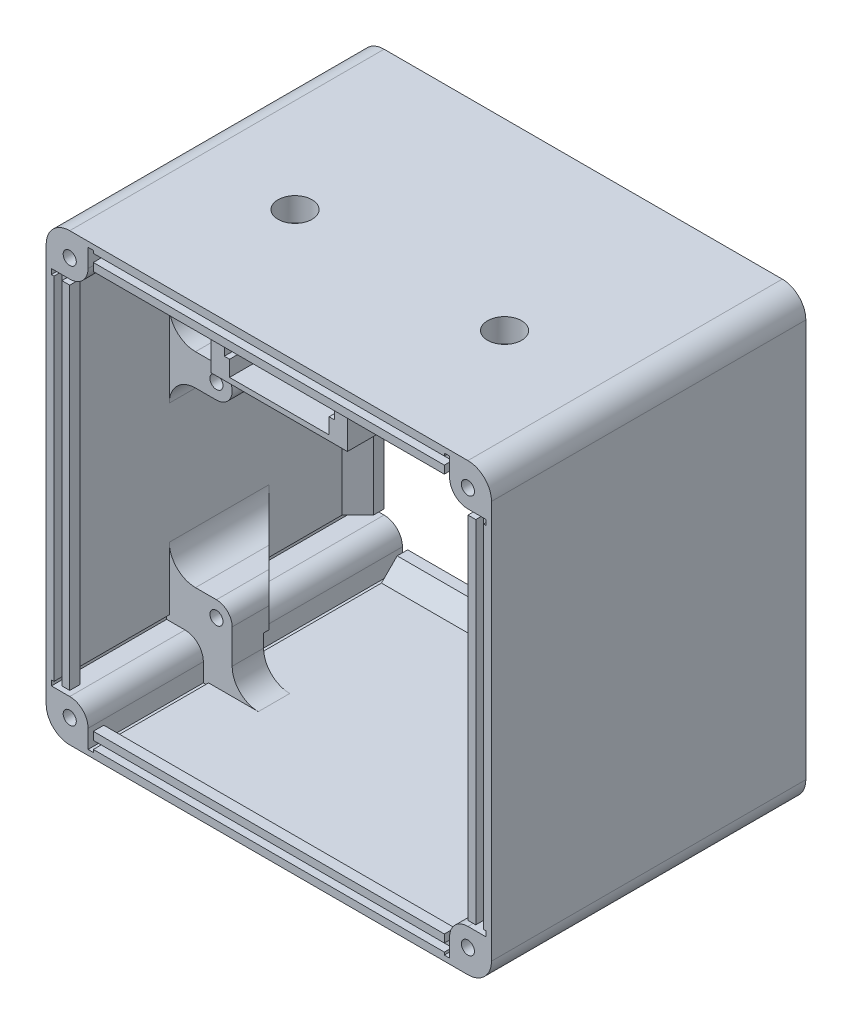
SolidWorks part; units mm, degrees
ref_plane "Front Plane" through (0, 0, 0) normal (0, 0, 1) x (1, 0, 0)
ref_plane "Top Plane" through (0, 0, 0) normal (0, 1, 0) x (1, 0, 0)
ref_plane "Right Plane" through (0, 0, 0) normal (1, 0, 0) x (0, 0, -1)
sketch "Sketch1" plane through (0, 0, 0) normal (0, 0, 1) x (1, 0, 0)
  line L1 (-42.5, -42.5) -> (42.5, -42.5)
  line L2 (-42.5, -42.5) -> (-42.5, 42.5)
  line L3 (-42.5, 42.5) -> (42.5, 42.5)
  line L4 (42.5, -42.5) -> (42.5, 42.5)
  line L5 (-42.5, -42.5) -> (42.5, 42.5) construction
  line L6 (-42.5, 42.5) -> (42.5, -42.5) construction
  point P0 (0, 0)
  dimension "D1" = 85
  dimension "D2" = 85
extrude "Boss-Extrude1" add sketch "Sketch1" along normal blind 60
sketch "Sketch8" plane through (0, 0, 0) normal (0, 0, -1) x (-1, 0, 0)
  line L14 (41, -41) -> (41, 41)
  line L15 (-41, -41) -> (41, -41)
  line L16 (-41, 41) -> (-41, -41)
  line L17 (41, 41) -> (-41, 41)
  line L18 (41, -36.5) -> (41, 36.5)
  line L19 (-36.5, -41) -> (36.5, -41)
  line L20 (-41, 36.5) -> (-41, -36.5)
  line L21 (36.5, 41) -> (-36.5, 41)
  arc A0 (-36.5, -41) -> (-41, -36.5) centre (-36.5, -36.5) cw
  arc A1 (41, -36.5) -> (36.5, -41) centre (36.5, -36.5) cw
  arc A2 (41, 36.5) -> (36.5, 41) centre (36.5, 36.5) ccw
  arc A3 (-41, 36.5) -> (-36.5, 41) centre (-36.5, 36.5) cw
  dimension "D2" = 4.5
  dimension "D1" = 1.5
extrude "Cut-Extrude4" cut sketch "Sketch8" against normal through all
fillet "Fillet4" radius 6 4 edges at (42.5, 42.5, 30) (42.5, -42.5, 30) (-42.5, 42.5, 30) (-42.5, -42.5, 30)
sketch "Sketch34" plane through (0, 0, 0) normal (0, 0, 1) x (1, 0, 0)
  line L0 (36.5, 42.5) -> (-36.5, 42.5) construction
  line L1 (-42.5, 36.5) -> (-42.5, -36.5) construction
  line L2 (-36.5, -42.5) -> (36.5, -42.5) construction
  line L3 (36.5, 42.5) -> (-36.5, 42.5)
  line L4 (42.5, -36.5) -> (42.5, 36.5)
  line L5 (36.5, 42.5) -> (-36.5, 42.5)
  line L6 (-42.5, 36.5) -> (-42.5, -36.5)
  line L7 (-36.5, -42.5) -> (36.5, -42.5)
  line L8 (42.5, -36.5) -> (42.5, 36.5)
  line L9 (36.5, 42.5) -> (-36.5, 42.5)
  line L10 (-42.5, 36.5) -> (-42.5, -36.5)
  line L11 (-36.5, -42.5) -> (36.5, -42.5)
  line L12 (-42.5, 36.5) -> (-42.5, -36.5)
  line L13 (-36.5, -42.5) -> (36.5, -42.5)
  line L14 (36.5, 38) -> (-36.5, 38)
  line L15 (-38, 36.5) -> (-38, -36.5)
  line L16 (-36.5, -38) -> (36.5, -38)
  line L17 (38, -36.5) -> (38, 36.5)
  arc A0 (-36.5, 42.5) -> (-42.5, 36.5) centre (-36.5, 36.5) ccw construction
  arc A1 (-42.5, -36.5) -> (-36.5, -42.5) centre (-36.5, -36.5) ccw construction
  arc A2 (36.5, -42.5) -> (42.5, -36.5) centre (36.5, -36.5) ccw construction
  arc A3 (-36.5, 42.5) -> (-42.5, 36.5) centre (-36.5, 36.5) ccw
  arc A4 (42.5, 36.5) -> (36.5, 42.5) centre (36.5, 36.5) ccw
  arc A5 (-36.5, 42.5) -> (-42.5, 36.5) centre (-36.5, 36.5) ccw
  arc A6 (-42.5, -36.5) -> (-36.5, -42.5) centre (-36.5, -36.5) ccw
  arc A7 (36.5, -42.5) -> (42.5, -36.5) centre (36.5, -36.5) ccw
  arc A8 (42.5, 36.5) -> (36.5, 42.5) centre (36.5, 36.5) ccw
  arc A9 (-36.5, 42.5) -> (-42.5, 36.5) centre (-36.5, 36.5) ccw
  arc A10 (-42.5, -36.5) -> (-36.5, -42.5) centre (-36.5, -36.5) ccw
  arc A11 (36.5, -42.5) -> (42.5, -36.5) centre (36.5, -36.5) ccw
  arc A12 (-42.5, -36.5) -> (-36.5, -42.5) centre (-36.5, -36.5) ccw
  arc A13 (36.5, -42.5) -> (42.5, -36.5) centre (36.5, -36.5) ccw
  arc A14 (-36.5, 38) -> (-38, 36.5) centre (-36.5, 36.5) ccw
  arc A15 (-38, -36.5) -> (-36.5, -38) centre (-36.5, -36.5) ccw
  arc A16 (36.5, -38) -> (38, -36.5) centre (36.5, -36.5) ccw
  arc A17 (38, 36.5) -> (36.5, 38) centre (36.5, 36.5) ccw
  dimension "D1" = 0
  dimension "D2" = 4.5
extrude "Boss-Extrude11" add sketch "Sketch34" along normal blind 2 contours L11 A11 L8 A8 L3 A3 L10 A10 A17 L17 A16 L16 A15 L15 A14 L14 region at (39.8926, 39.8926, 0)
sketch "Sketch35" plane through (0, 0, 0) normal (0, 0, -1) x (-1, 0, 0)
  line L25 (-36.5, -41) -> (36.5, -41)
  line L26 (41, -36.5) -> (41, 36.5)
  line L27 (36.5, 41) -> (-36.5, 41)
  line L28 (-41, 36.5) -> (-41, -36.5)
  line L29 (-36.5, -41) -> (36.5, -41)
  line L30 (41, -36.5) -> (41, 36.5)
  line L31 (36.5, 41) -> (-36.5, 41)
  line L32 (-41, 36.5) -> (-41, -36.5)
  arc A20 (-41, -36.5) -> (-36.5, -41) centre (-36.5, -36.5) ccw
  arc A21 (36.5, -41) -> (41, -36.5) centre (36.5, -36.5) ccw
  arc A22 (41, 36.5) -> (36.5, 41) centre (36.5, 36.5) ccw
  arc A23 (-36.5, 41) -> (-41, 36.5) centre (-36.5, 36.5) ccw
  arc A24 (-41, -36.5) -> (-36.5, -41) centre (-36.5, -36.5) ccw
  arc A25 (36.5, -41) -> (41, -36.5) centre (36.5, -36.5) ccw
  arc A26 (41, 36.5) -> (36.5, 41) centre (36.5, 36.5) ccw
  arc A27 (-36.5, 41) -> (-41, 36.5) centre (-36.5, 36.5) ccw
  dimension "D1" = 1.5
extrude "Cut-Extrude-Thin2" cut sketch "Sketch35" against normal blind 1.5 thin thin type one direction reverse wall 1.5
ref_plane "Plane1" through (0, 0, 30) normal (0, 0, 1) x (1, 0, 0)
mirror "Mirror8" about plane through (0, 0, 30) normal (0, 0, 1) of "Boss-Extrude11", "Cut-Extrude-Thin2"
chamfer "Chamfer5" distance 3 angle 45 16 edges at (0, -41, 58) (39.682, -39.682, 58) (-39.682, -39.682, 58) (41, 0, 58) (-41, 0, 58) (39.682, 39.682, 58) (-39.682, 39.682, 58) (0, 41, 58) (0, -41, 2) (-39.682, -39.682, 2) (39.682, -39.682, 2) (-41, 0, 2) (41, 0, 2) (-39.682, 39.682, 2) (39.682, 39.682, 2) (0, 41, 2)
sketch "Sketch14" plane through (0, 0, 60) normal (0, 0, 1) x (1, 0, 0)
  line L0 (-42.5, 36.5) -> (-42.5, -36.5) construction
  line L1 (-38, 33.5) -> (-42.5, 33.5)
  line L2 (-42.5, 36.5) -> (-42.5, -36.5) construction
  line L3 (-42.5, 33.5) -> (-42.5, 38)
  line L4 (-38, 42.5) -> (-33.5, 42.5)
  line L5 (-33.5, 42.5) -> (-33.5, 38)
  arc A0 (-38, 42.5) -> (-42.5, 38) centre (-38, 38) ccw
  arc A2 (-38, 33.5) -> (-33.5, 38) centre (-38, 38) ccw
  dimension "D1" = 38
  dimension "D2" = 38
extrude "Boss-Extrude6" add sketch "Sketch14" against normal up to surface (60 mm away) up to face at (0, 0, 0)
sketch "Sketch15" plane through (0, 0, 0) normal (0, 0, -1) x (-1, 0, 0)
  circle A0 centre (38, 38) radius 1.25
  arc A1 (33.5, 38) -> (38, 33.5) centre (38, 38) ccw construction
  dimension "D1" = 2.5
extrude "Cut-Extrude7" cut sketch "Sketch15" against normal through all
sketch "Sketch28" plane through (0, 0, 0) normal (0, 0, -1) x (-1, 0, 0)
  line L0 (33.5, 38) -> (33.5, 41.5) construction
  line L3 (41.5, 33.5) -> (38, 33.5) construction
  line L4 (33.5, 38) -> (33.5, 41.5)
  line L5 (41.5, 33.5) -> (38, 33.5)
  arc A0 (33.5, 38) -> (38, 33.5) centre (38, 38) ccw construction
  arc A1 (33.5, 38) -> (38, 33.5) centre (38, 38) ccw
extrude "Cut-Extrude-Thin1" cut sketch "Sketch28" against normal through all thin thin type one direction wall 1
mirror "Mirror3" about plane through (0, 0, 0) normal (1, 0, 0) of "Cut-Extrude-Thin1", "Boss-Extrude6", "Cut-Extrude7"
mirror "Mirror4" about plane through (0, 0, 0) normal (0, 1, 0) of "Mirror3"
sketch "Sketch23" plane through (0, 0, 0) normal (0, 0, -1) x (-1, 0, 0)
  line L1 (-38.5, -41.5) -> (-29, -41.5)
  line L2 (-41.5, -38.5) -> (-41.5, -26.5)
  line L3 (-41.5, -26.5) -> (-32, -26.5)
  line L4 (-29, -41.5) -> (-29, -29.5)
  line L5 (-41.5, 12.5) -> (-32, 12.5)
  line L6 (-41.5, 12.5) -> (-41.5, 6.5)
  line L7 (-41.5, 6.5) -> (-32, 6.5)
  line L10 (-41.5, 34.5) -> (-41.5, -34.5) construction
  line L11 (-34.5, -41.5) -> (34.5, -41.5) construction
  arc A0 (-32, 12.5) -> (-32, 6.5) centre (-32, 9.5) cw
  arc A1 (-32, -26.5) -> (-29, -29.5) centre (-32, -29.5) cw
  arc A2 (-38.5, -41.5) -> (-41.5, -38.5) centre (-38.5, -38.5) cw
  point P21 (-41.5, -41.5)
  dimension "D1" = 3
  dimension "D5" = 3
  dimension "D2" = 32
  dimension "D3" = 6
  dimension "D4" = 12
  dimension "39" = 39
extrude "Boss-Extrude8" add sketch "Sketch23" against normal blind 6 from offset 32 offset against normal yes
sketch "Sketch25" plane through (0, 0, 38) normal (0, 0, 1) x (1, 0, 0)
  circle A0 centre (32, -29.5) radius 1.25
  circle A1 centre (32, 9.5) radius 1.25
  dimension "D1" = 2.5
extrude "Cut-Extrude10" cut sketch "Sketch25" against normal blind 5
mirror "Mirror6" about plane through (0, 0, 0) normal (1, 0, 0) of "Boss-Extrude8", "Cut-Extrude10"
chamfer "Chamfer1" distance 13 angle 45 4 edges at (41, -30, 32) (41, 9.5, 32) (-41, 9.5, 32) (-41, -30, 32)
fillet "Fillet5" radius 5 8 edges at (29, -41, 35) (41, -26.5, 28.5) (41, 12.5, 28.5) (41, 6.5, 28.5) (-41, 6.5, 28.5) (-41, 12.5, 28.5) (-41, -26.5, 28.5) (-29, -41, 35) tangent propagation no
sketch "Sketch29" plane through (0, 42.5, 0) normal (0, 1, 0) x (1, 0, 0)
  line L0 (-20, -35) -> (20, -35) construction
  line L1 (0, 0) -> (0, -35) construction
  circle A0 centre (-20, -35) radius 3.25
  circle A1 centre (20, -35) radius 3.25
  dimension "D3" = 6.5
  dimension "D1" = 35
  dimension "D2" = 40
extrude "Cut-Extrude11" cut sketch "Sketch29" against normal up to next
sketch "Sketch30" plane through (0, 41, 0) normal (0, -1, 0) x (1, 0, 0)
  line L0 (-20, 28.5) -> (20, 28.5)
  line L1 (-20, 41.5) -> (20, 41.5)
  arc A0 (-20, 41.5) -> (-20, 28.5) centre (-20, 35) ccw
  arc A1 (20, 28.5) -> (20, 41.5) centre (20, 35) ccw
  circle A2 centre (-20, 35) radius 3.25 construction
  circle A3 centre (20, 35) radius 3.25 construction
  circle A4 centre (-20, 35) radius 3.25
  circle A5 centre (20, 35) radius 3.25
  dimension "D1" = 13
extrude "Boss-Extrude9" add sketch "Sketch30" along normal blind 3
sketch "Sketch31" plane through (0, 0, 60) normal (0, 0, 1) x (1, 0, 0)
  line L0 (33.5, 41.5) -> (34.5, 41.5) construction
  line L1 (-13, 41.5) -> (13, 41.5)
  line L2 (-13, 41.5) -> (-13, 30.5)
  line L3 (-13, 30.5) -> (13, 30.5)
  line L4 (13, 41.5) -> (13, 30.5)
  line L5 (0, 30.5) -> (0, 0) construction
  dimension "D1" = 26
  dimension "D2" = 11
extrude "Boss-Extrude10" add sketch "Sketch31" against normal blind 30 from offset 2 offset against normal yes
sketch "Sketch32" plane through (0, 0, 58) normal (0, 0, 1) x (1, 0, 0)
  line L1 (-9.5, 31.5) -> (9.5, 31.5)
  line L2 (-9.5, 31.5) -> (-9.5, 41)
  line L3 (-9.5, 41) -> (9.5, 41)
  line L4 (9.5, 31.5) -> (9.5, 41)
  line L5 (0, 41) -> (0, 31.5) construction
  line L6 (13, 41) -> (-13, 41) construction
  line L7 (-13, 30.5) -> (13, 30.5) construction
  dimension "D1" = 9.5
  dimension "D2" = 19
  dimension "D3" = 1
extrude "Cut-Extrude12" cut sketch "Sketch32" against normal blind 26
sketch "Sketch33" plane through (0, 0, 58) normal (0, 0, 1) x (1, 0, 0)
  line L0 (0, 34.5) -> (0, 41) construction
  line L1 (-10.5, 36) -> (10.5, 36)
  line L2 (-10.5, 36) -> (-10.5, 34.5)
  line L3 (-10.5, 34.5) -> (10.5, 34.5)
  line L4 (10.5, 36) -> (10.5, 34.5)
  line L5 (9.5, 41) -> (-9.5, 41) construction
  line L6 (-9.5, 31.5) -> (9.5, 31.5) construction
  dimension "D1" = 21
  dimension "2.5" = 1.5
  dimension "D2" = 3
extrude "Cut-Extrude13" cut sketch "Sketch33" against normal up to surface (26 mm away) up to face at (0, 36.25, 32)
chamfer "Chamfer3" distance 11 angle 45 1 edges at (0, 41, 28)
chamfer "Chamfer2" distance 3 angle 45 8 edges at (26.5, 41, 35) (-26.5, 41, 35) (16.5, 41, 28.5) (-16.5, 41, 41.5) (-13, 41, 48.25) (-13, 41, 22.75) (13, 41, 22.75) (13, 41, 48.25)
